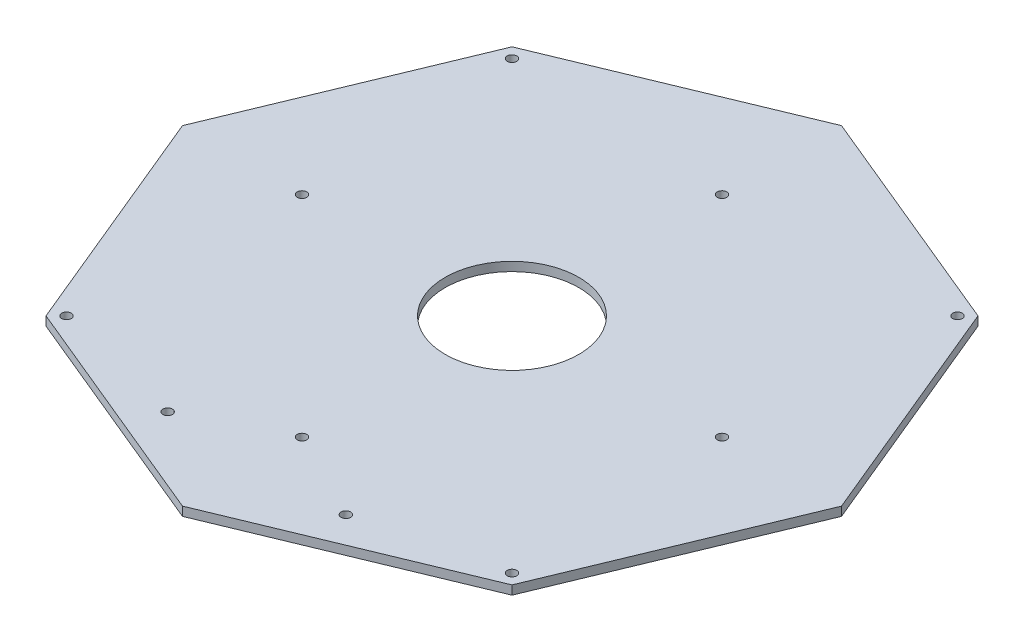
SolidWorks part; units mm, degrees
ref_plane "Front Plane" through (0, 0, 0) normal (0, 0, 1) x (1, 0, 0)
ref_plane "Top Plane" through (0, 0, 0) normal (0, 1, 0) x (1, 0, 0)
ref_plane "Right Plane" through (0, 0, 0) normal (1, 0, 0) x (0, 0, -1)
sketch "Sketch1" plane through (0, 0, 0) normal (0, 1, 0) x (1, 0, 0)
  line L0 (0, -110.9452) -> (78.4501, -78.4501)
  line L7 (0, 110.9452) -> (-78.4501, 78.4501)
  line L8 (-78.4501, 78.4501) -> (-110.9452, 0)
  line L9 (-110.9452, 0) -> (-78.4501, -78.4501)
  line L10 (-78.4501, -78.4501) -> (0, -110.9452)
  line L11 (78.4501, -78.4501) -> (110.9452, 0)
  line L12 (110.9452, 0) -> (78.4501, 78.4501)
  line L13 (78.4501, 78.4501) -> (0, 110.9452)
  circle A0 centre (0, 0) radius 102.5 construction
  dimension "D1" = 205
extrude "Boss-Extrude2" add sketch "Sketch1" along normal blind 3
sketch "Sketch3" plane through (0, 3, 0) normal (0, 1, 0) x (1, 0, 0)
  line L0 (-110.9452, 0) -> (110.9452, 0) construction
  line L1 (0, 110.9452) -> (0, -110.9452) construction
  line L2 (-75, -75) -> (0, 0) construction
  circle A0 centre (-75, -75) radius 1.6
  circle A1 centre (75, -75) radius 1.6
  circle A2 centre (75, 75) radius 1.6
  circle A3 centre (-75, 75) radius 1.6
  circle A4 centre (-70.7107, 0) radius 1.6
  circle A5 centre (0, 70.7107) radius 1.6
  circle A6 centre (70.7107, 0) radius 1.6
  circle A7 centre (0, -70.7107) radius 1.6
  point P28 (0, 0)
  dimension "D1" = 3.2
  dimension "D4" = 3.2
  dimension "D2" = 150
  dimension "D3" = 150
  dimension "D6" = 100
  dimension "D5" = 4
extrude "Cut-Extrude3" cut sketch "Sketch3" against normal through all both and the other way through all
sketch "Sketch4" plane through (0, 3, 0) normal (0, 1, 0) x (1, 0, 0)
  line L0 (0, -110.9452) -> (0, -85.9452) construction
  circle A0 centre (-30, -85.9452) radius 1.6
  circle A1 centre (30, -85.9452) radius 1.6
  dimension "D1" = 3.2
  dimension "D2" = 60
  dimension "D3" = 25
extrude "Cut-Extrude4" cut sketch "Sketch4" against normal through all both and the other way through all
sketch "Sketch5" plane through (0, 3, 0) normal (0, 1, 0) x (1, 0, 0)
  line L0 (0, 0) -> (-78.4501, -78.4501) construction
  circle A0 centre (-82.7782, -82.7782) radius 1.6
  circle A6 centre (-75, -75) radius 1.6 construction
  circle A7 centre (-82.7782, 82.7782) radius 1.6
  circle A8 centre (82.7782, 82.7782) radius 1.6
  circle A9 centre (82.7782, -82.7782) radius 1.6
  point P18 (0, 0)
  point P21 (0, 0)
  dimension "D1" = 3.2
  dimension "D2" = 4
  dimension "D3" = 11
sketch "Sketch6" plane through (0, 3, 0) normal (0, 1, 0) x (1, 0, 0)
  circle A0 centre (0, 0) radius 22.5
  dimension "D1" = 45
extrude "Cut-Extrude6" cut sketch "Sketch6" against normal through all both and the other way through all
